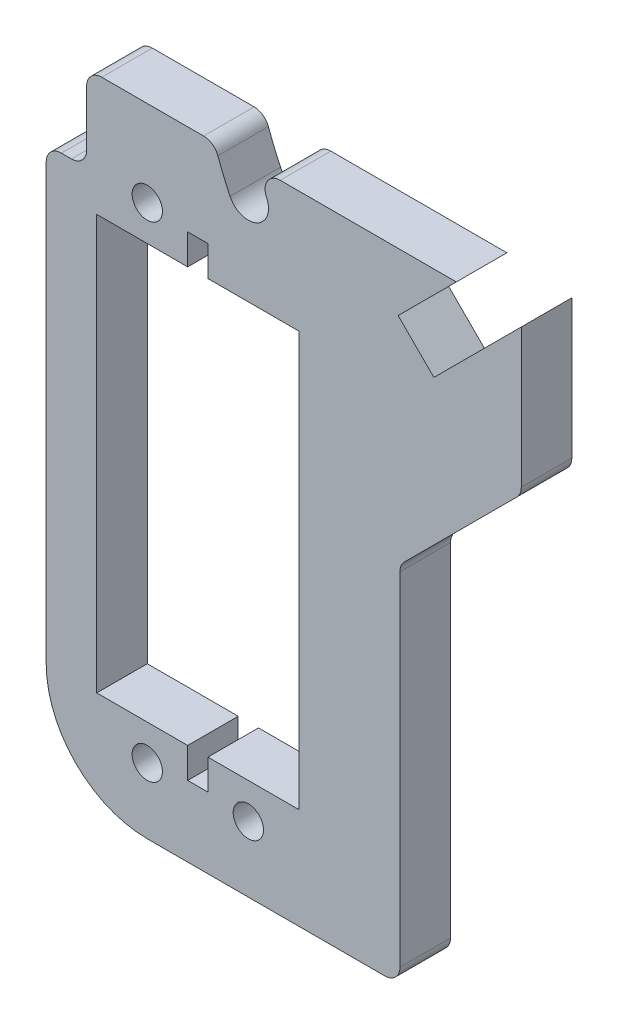
SolidWorks part; units mm, degrees
ref_plane "Plan de face" through (0, 0, 0) normal (0, 0, 1) x (1, 0, 0)
ref_plane "Plan de dessus" through (0, 0, 0) normal (0, 1, 0) x (1, 0, 0)
ref_plane "Plan de droite" through (0, 0, 0) normal (1, 0, 0) x (0, 0, -1)
sketch "Esquisse1" plane through (0, 0, 0) normal (0, 0, 1) x (1, 0, 0)
  line L0 (15, 10) -> (15, 51) construction
  line L1 (0, 0) -> (35, 0)
  line L2 (0, 0) -> (0, 54.5)
  line L3 (4, 63) -> (16.6453, 63)
  line L4 (40.5763, 63) -> (34.8194, 57.2431)
  line L5 (14, 51) -> (5, 51)
  line L6 (20.8844, 63) -> (40.5763, 63)
  line L7 (25, 10) -> (16, 10)
  line L8 (5, 51) -> (5, 10)
  line L9 (5, 30.5) -> (25, 30.5) construction
  line L10 (25, 10) -> (25, 51)
  line L11 (25, 51) -> (16, 51)
  line L13 (47, 48) -> (47, 63)
  line L14 (47, 48) -> (35, 36)
  line L15 (34.8194, 57.2431) -> (38.3549, 53.7075)
  line L16 (38.3549, 53.7075) -> (47.6474, 63)
  line L17 (47.6474, 63) -> (47, 63)
  line L18 (16, 10) -> (16, 7)
  line L19 (14, 10) -> (5, 10)
  line L20 (14, 51) -> (14, 54)
  line L21 (14, 54) -> (16, 54)
  line L22 (16, 51) -> (16, 54)
  line L23 (14, 7) -> (16, 7)
  line L24 (14, 10) -> (14, 7)
  line L26 (35, 36) -> (35, 0)
  line L27 (43.3047, 58.6573) -> (45.426, 60.7786) construction
  line L28 (0, 54.5) -> (4, 54.5)
  line L29 (4, 63) -> (4, 54.5)
  line L31 (34.8194, 57.2431) -> (38.3549, 53.7075) construction
  circle A0 centre (10, 54.5) radius 1.5
  circle A1 centre (20, 54.5) radius 1.5 construction
  circle A2 centre (20, 6.5) radius 1.5
  circle A3 centre (10, 6.5) radius 1.5
  arc A4 (18.395, 64.1001) -> (19.9935, 60) centre (46.8198, 72.8198) ccw construction
  arc A5 (16.6453, 63) -> (18.1889, 59.1376) centre (46.8198, 72.8198) ccw
  arc A6 (20.8844, 63) -> (21.798, 60.8624) centre (46.8198, 72.8198) ccw
  arc A8 (18.1889, 59.1376) -> (21.798, 60.8624) centre (19.9935, 60) ccw
  arc A10 (18.1889, 59.1376) -> (21.8005, 60.8571) centre (19.9935, 60) ccw construction
  point P45 (14.6071, 61.4344)
  dimension "D6" = 3.5
  dimension "D8" = 3
  dimension "D11" = 2
  dimension "D16" = 27.7321
  dimension "D17" = 31.7321
  dimension "D1" = 20
  dimension "D2" = 41
  dimension "D3" = 10
  dimension "D4" = 12
  dimension "D5" = 5
  dimension "D7" = 5
  dimension "D9" = 22
  dimension "D10" = 5
  dimension "D12" = 2
  dimension "D13" = 3
  dimension "D14" = 8.5
  dimension "D15" = 4
  dimension "D18" = 10
  dimension "D20" = 15
extrude "Boss.-Extru.1" add sketch "Esquisse1" along normal blind 5 contours L3 L29 L28 L2 L1 L13 L4 L15 L16 L6 L24 L19 L8 L5 L20 L21 L22 L11 L10 L7 L18 L23 A0 A2 A3 region at (0.786, 27.25, 0)
fillet "Congé2" radius 10 1 edges at (0, 0, 2.5)
fillet "Congé3" radius 1.5 8 edges at (4, 54.5, 2.5) (0, 54.5, 2.5) (4, 63, 2.5) (20.8844, 63, 2.5) (16.6453, 63, 2.5) (47, 48, 2.5) (35, 0, 2.5) (35, 36, 2.5)
